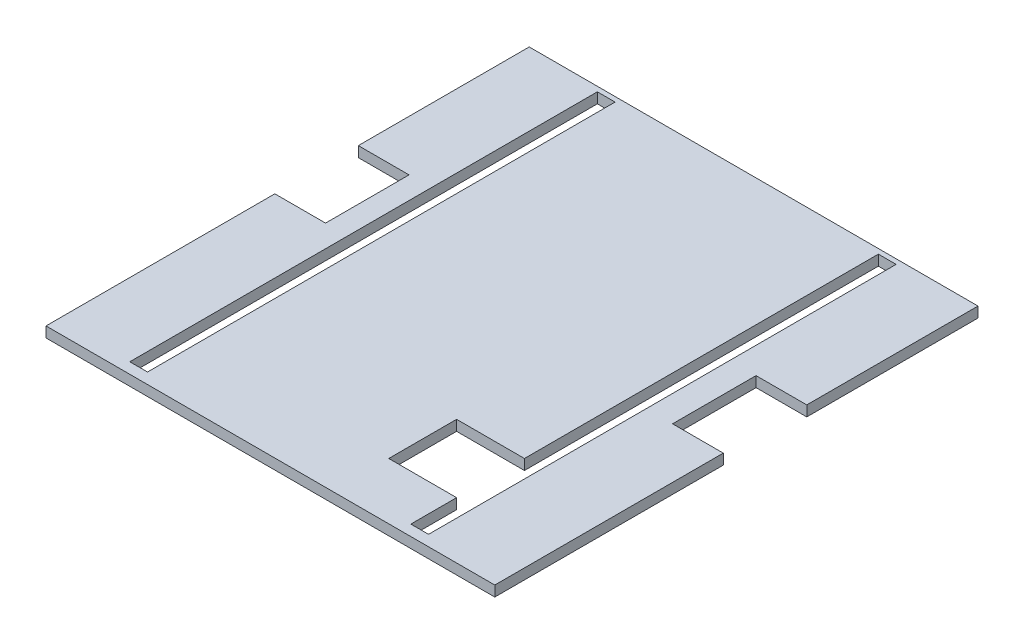
SolidWorks part; units mm, degrees
ref_plane "Front Plane" through (0, 0, 0) normal (0, 0, 1) x (1, 0, 0)
ref_plane "Top Plane" through (0, 0, 0) normal (0, 1, 0) x (1, 0, 0)
ref_plane "Right Plane" through (0, 0, 0) normal (1, 0, 0) x (0, 0, -1)
sketch "Sketch1" plane through (0, 0, 0) normal (0, 1, 0) x (1, 0, 0)
  line L1 (5911.0841, -8489.3124) -> (6341.0841, -8489.3124)
  line L2 (5911.0841, -8489.3124) -> (5911.0841, -8952.3124)
  line L3 (5911.0841, -8952.3124) -> (6341.0841, -8952.3124)
  line L4 (6341.0841, -8489.3124) -> (6341.0841, -8952.3124)
  dimension "D1" = 463
  dimension "D2" = 430
extrude "Boss-Extrude1" add sketch "Sketch1" along normal blind 10
sketch "Sketch2" plane through (0, 10, 0) normal (0, 1, 0) x (1, 0, 0)
  line L0 (5911.0841, -8489.3124) -> (5911.0841, -8952.3124) construction
  line L1 (5959.6841, -8733.0598) -> (5911.0841, -8733.0598)
  line L2 (5959.6841, -8733.0598) -> (5959.6841, -8653.0598)
  line L3 (5959.6841, -8653.0598) -> (5911.0841, -8653.0598)
  line L4 (5911.0841, -8733.0598) -> (5911.0841, -8653.0598)
  line L9 (6341.0841, -8952.3124) -> (6341.0841, -8489.3124) construction
  line L10 (6341.0841, -8733.3844) -> (6292.4841, -8733.3844)
  line L11 (6341.0841, -8733.3844) -> (6341.0841, -8653.3844)
  line L12 (6341.0841, -8653.3844) -> (6292.4841, -8653.3844)
  line L13 (6292.4841, -8733.3844) -> (6292.4841, -8653.3844)
  dimension "D1" = 48.6
  dimension "D2" = 80
  dimension "D3" = 80
  dimension "D4" = 48.6
extrude "Cut-Extrude1" cut sketch "Sketch2" against normal blind 10
sketch "Sketch3" plane through (0, 10, 0) normal (0, 1, 0) x (1, 0, 0)
  line L1 (6267.2928, -8941.975) -> (6250.2928, -8941.975)
  line L2 (6267.2928, -8941.975) -> (6267.2928, -8493.975)
  line L3 (6267.2928, -8493.975) -> (6250.2928, -8493.975)
  line L4 (6250.2928, -8941.975) -> (6250.2928, -8493.975)
  line L5 (5980.9647, -8493.9103) -> (5997.9647, -8493.9103)
  line L10 (5980.9647, -8493.9103) -> (5980.9647, -8941.9103)
  line L11 (5980.9647, -8941.9103) -> (5997.9647, -8941.9103)
  line L12 (5997.9647, -8493.9103) -> (5997.9647, -8941.9103)
  dimension "D1" = 17
  dimension "D2" = 448
  dimension "D3" = 17
  dimension "D4" = 448
extrude "Cut-Extrude2" cut sketch "Sketch3" against normal blind 10
sketch "Sketch4" plane through (0, 10, 0) normal (0, 1, 0) x (1, 0, 0)
  line L0 (6250.2928, -8493.975) -> (6250.2928, -8941.975) construction
  line L1 (6250.2928, -8898.0965) -> (6185.2928, -8898.0965)
  line L2 (6250.2928, -8898.0965) -> (6250.2928, -8833.0965)
  line L3 (6250.2928, -8833.0965) -> (6185.2928, -8833.0965)
  line L4 (6185.2928, -8898.0965) -> (6185.2928, -8833.0965)
  dimension "D1" = 65
  dimension "D2" = 65
extrude "Cut-Extrude3" cut sketch "Sketch4" against normal blind 10
ref_plane "Plane1" through (6126.0841, 0, 0) normal (-1, 0, 0) x (0, 0, 1)
sketch "Sketch5" plane through (6126.0841, 0, 0) normal (-1, 0, 0) x (0, 0, 1)
  line L1 (8395.6862, 142.8464) -> (9031.9061, 142.8464)
  line L2 (8395.6862, 142.8464) -> (8395.6862, -229.0644)
  line L3 (8395.6862, -229.0644) -> (9031.9061, -229.0644)
  line L4 (9031.9061, 142.8464) -> (9031.9061, -229.0644)
